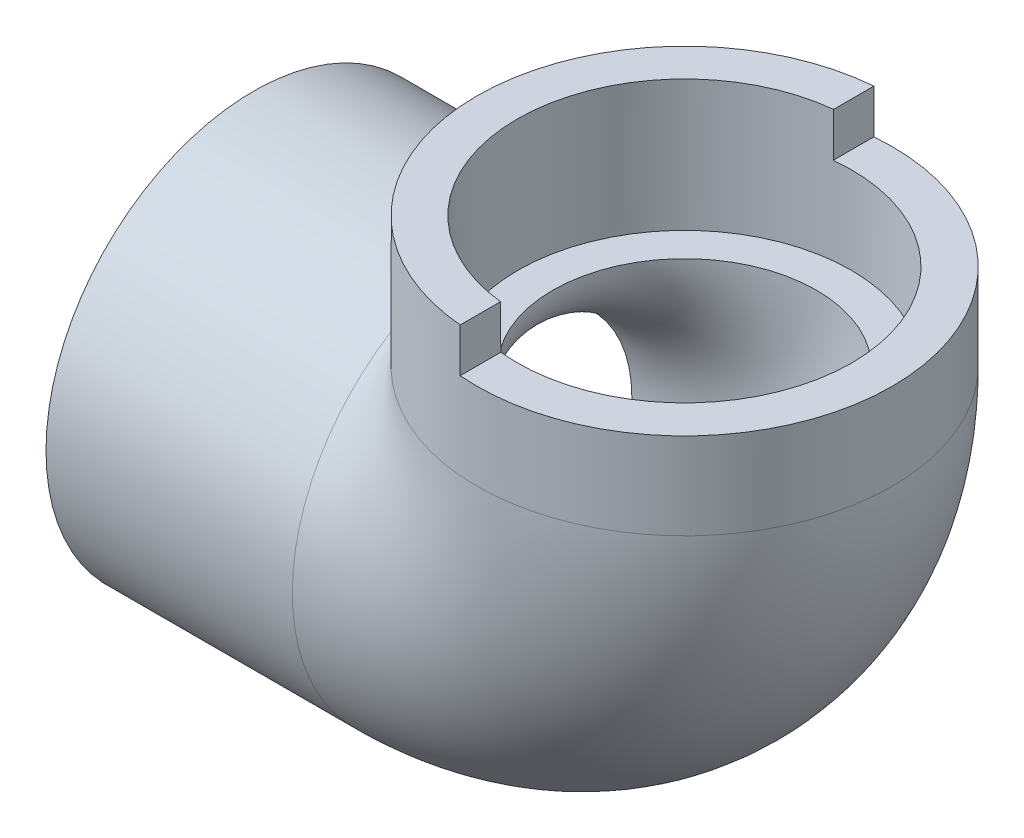
SolidWorks part; units mm, degrees
ref_plane "Front Plane" through (0, 0, 0) normal (0, 0, 1) x (1, 0, 0)
ref_plane "Top Plane" through (0, 0, 0) normal (0, 1, 0) x (1, 0, 0)
ref_plane "Right Plane" through (0, 0, 0) normal (1, 0, 0) x (0, 0, -1)
sketch "Sketch0" plane through (0, 0, 0) normal (0, 0, 1) x (1, 0, 0)
  line L0 (-62.23, 0) -> (0, 0) construction
  line L1 (0, 0) -> (0, 62.23) construction
  line L2 (-26.67, 0) -> (0, 0) construction
  line L3 (0, 0) -> (0, 26.67) construction
  line L4 (-62.23, 29.972) -> (-62.23, -29.972) construction
  line L5 (-26.67, 24.0538) -> (-62.23, 24.2824) construction
  line L6 (-26.67, 24.0538) -> (-26.67, -24.0538) construction
  line L7 (-26.67, -24.0538) -> (-62.23, -24.2824) construction
  line L8 (-62.23, 24.2824) -> (-62.23, -24.2824) construction
  line L9 (-29.972, 62.23) -> (29.972, 62.23) construction
  line L10 (-24.2824, 62.23) -> (24.2824, 62.23) construction
  line L11 (24.2824, 62.23) -> (24.0538, 26.67) construction
  line L12 (24.0538, 26.67) -> (-24.0538, 26.67) construction
  line L13 (-24.0538, 26.67) -> (-24.2824, 62.23) construction
  line L14 (-26.67, 19.05) -> (-26.67, -19.05) construction
  line L18 (-19.05, 26.67) -> (19.05, 26.67) construction
  dimension "H" = 62.23
  dimension "G" = 26.67
  dimension "M" = 59.944
  dimension "OD A" = 48.5648
  dimension "OD B" = 48.1076
  dimension "ID" = 38.1
sketch "Sketch1" plane through (0, 0, 0) normal (0, 0, 1) x (1, 0, 0)
  line L0 (-62.23, 0) -> (0, 0) construction
  line L1 (-62.23, 0) -> (0, 0) construction
  line L3 (-62.23, -29.972) -> (-26.67, -29.972)
  line L4 (-62.23, -29.972) -> (-62.23, -24.2824)
  line L5 (-62.23, -24.2824) -> (-26.67, -24.0538)
  line L6 (-26.67, -29.972) -> (-26.67, -24.0538)
revolve "Revolve1" add sketch "Sketch1" angle 360 about L1
sketch "Sketch2" plane through (0, 0, 0) normal (0, 0, 1) x (1, 0, 0)
  line L0 (24.2824, 62.23) -> (24.0538, 26.67)
  line L1 (24.0538, 26.67) -> (29.972, 26.67)
  line L2 (29.972, 26.67) -> (29.972, 62.23)
  line L3 (29.972, 62.23) -> (24.2824, 62.23)
  line L4 (0, 0) -> (0, 62.23) construction
  line L5 (0, 0) -> (0, 62.23) construction
revolve "Revolve2" add sketch "Sketch2" angle 360 about L5
sketch "Sketch3" plane through (-26.67, 0, 0) normal (1, 0, 0) x (0, 0, -1)
  circle A0 centre (0, 0) radius 19.05
  circle A1 centre (0, 0) radius 29.972
sketch "Sketch4" plane through (0, 0, 0) normal (0, 0, 1) x (1, 0, 0)
  line L0 (-62.23, 0) -> (0, 0) construction
  line L1 (0, 0) -> (0, 62.23) construction
  line L2 (-62.23, 0) -> (-26.67, 0) construction
  line L3 (0, 26.67) -> (0, 62.23) construction
  arc A0 (-26.67, 0) -> (0, 26.67) centre (-26.67, 26.67) ccw
sweep "Sweep1" add profiles "Sketch3" path "Sketch4"
other "CPoint1" parameters "Diameter"=38.1, "StubLength"=28.575
ref_axis "Axis1" through (-36.67, 0, 0) along (1, 0, 0)
other "CPoint2" parameters "Diameter"=38.1, "StubLength"=57.15
ref_axis "Axis2" through (0, 36.67, 0) along (0, -1, 0)
other "RPoint1"
sketch "Sketch6" plane through (0, 0, 0) normal (0, 0, 1) x (1, 0, 0)
  line L0 (0, 0) -> (-54.8637, 0) construction
  line L1 (-62.23, 0) -> (0, 0) construction
  line L3 (-30.1243, 15.24) -> (-79.6032, 15.24)
  line L4 (-30.1243, 15.24) -> (-30.1243, -15.24)
  line L5 (-30.1243, -15.24) -> (-79.6032, -15.24)
  line L6 (-79.6032, 15.24) -> (-79.6032, -15.24)
  line L7 (-30.1243, 15.24) -> (-79.6032, -15.24) construction
  line L8 (-30.1243, -15.24) -> (-79.6032, 15.24) construction
  dimension "D1" = 30.48
extrude "Cut-Extrude2" cut sketch "Sketch6" against normal through all
sketch "Sketch7" plane through (0, 0, 0) normal (1, 0, 0) x (0, 0, -1)
  line L0 (0, 0) -> (0, 42.3418) construction
  line L1 (0, 0) -> (0, 62.23) construction
  line L3 (-31.75, 39.1668) -> (31.75, 39.1668)
  line L4 (-31.75, 39.1668) -> (-31.75, 45.5168)
  line L5 (-31.75, 45.5168) -> (31.75, 45.5168)
  line L6 (31.75, 39.1668) -> (31.75, 45.5168)
  line L7 (-31.75, 39.1668) -> (31.75, 45.5168) construction
  line L8 (-31.75, 45.5168) -> (31.75, 39.1668) construction
  dimension "D1" = 63.5
  dimension "D2" = 6.35
  dimension "D3" = 42.3418
extrude "Cut-Extrude3" cut sketch "Sketch7" against normal blind 2.54 and the other way through all
sketch "Sketch8" plane through (0, 45.5168, 0) normal (0, -1, 0) x (1, 0, 0)
  circle A0 centre (0, 0) radius 43.6122
extrude "Cut-Extrude4" cut sketch "Sketch8" against normal through all
